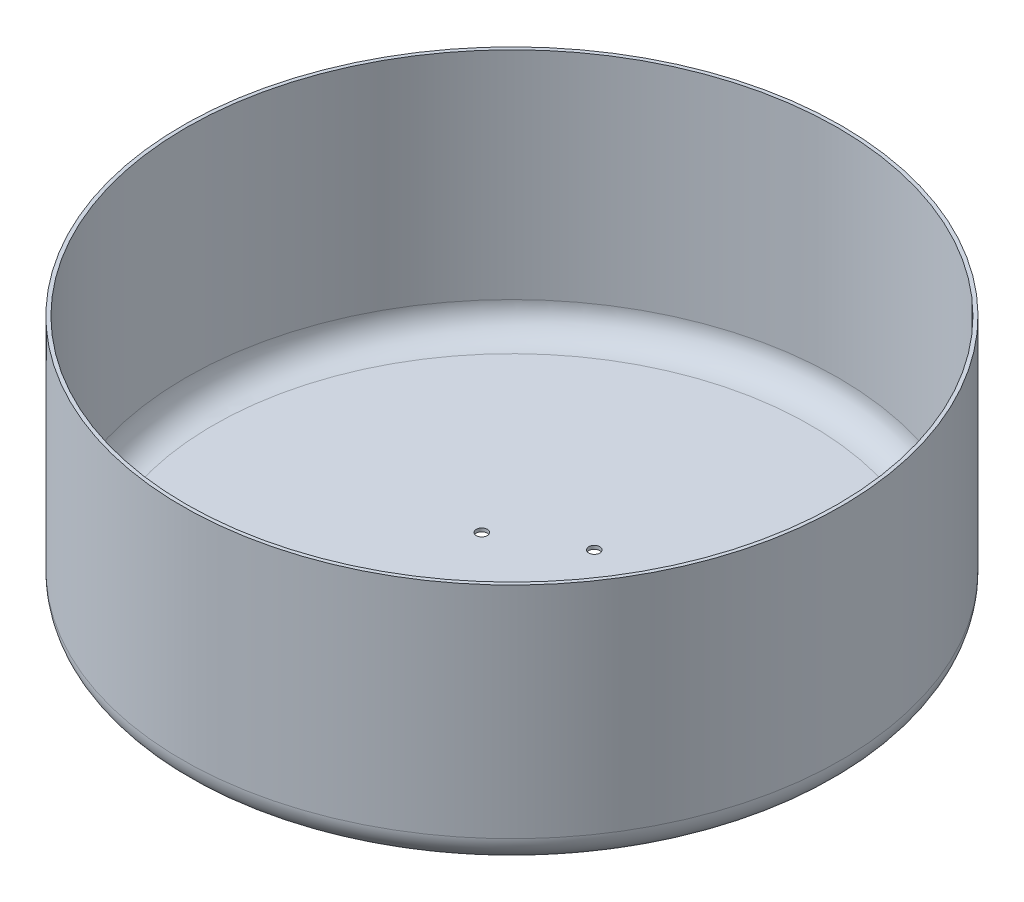
SolidWorks part; units mm, degrees
material "2024-T4"
ref_plane "Front Plane" through (0, 0, 0) normal (0, 0, 1) x (1, 0, 0)
ref_plane "Top Plane" through (0, 0, 0) normal (0, 1, 0) x (1, 0, 0)
ref_plane "Right Plane" through (0, 0, 0) normal (1, 0, 0) x (0, 0, -1)
sketch "Sketch1" plane through (0, 0, 0) normal (0, 0, 1) x (1, 0, 0)
  line L0 (0, 0) -> (0, 114.3) construction
  line L1 (0, 0) -> (152.4, 0)
  line L2 (152.4, 0) -> (152.4, 114.3)
  line L3 (152.4, 114.3) -> (150.749, 114.3)
  line L4 (150.749, 114.3) -> (150.749, 1.5748)
  line L5 (150.749, 1.5748) -> (0, 1.5748)
  line L6 (0, 1.5748) -> (0, 0)
  dimension "D1" = 114.3
  dimension "D2" = 1.5748
  dimension "D3" = 1.651
  dimension "D4" = 114.3
  dimension "D6" = 152.4
revolve "Revolve1" add sketch "Sketch1" angle 360 about L0
fillet "Fillet1" radius 12.7 2 edges at (0, 0, -152.4) (0, 1.5748, -150.749)
hole_wizard "#10 Clearance Hole1" positions "Sketch3" profile "Sketch2" hole size "#10" standard "Ansi Inch" end condition through all
sketch "Sketch3" plane through (0, 0, 0) normal (0, -1, 0) x (1, 0, 0)
  point P0 (0, 38.1)
  point P9 (32.9956, 19.05)
  point P10 (32.9956, -19.05)
  point P11 (0, -38.1)
  point P12 (-32.9956, -19.05)
  point P13 (-32.9956, 19.05)
  dimension "D1" = 38.1
  dimension "D2" = 6
sketch "Sketch2" plane through (0, 0, 38.1) normal (1, 0, 0) x (0, 0, -1)
  line L0 (0, 0) -> (0, 114.3)
  line L1 (0, 114.3) -> (2.5527, 114.3)
  line L2 (2.5527, 114.3) -> (2.5527, 0)
  line L5 (2.5527, 0) -> (0, 0)
  line L11 (0, -6.35) -> (0, 107.95) construction
  dimension "Thru Hole Dia." = 5.1054
  dimension "Thru Hole Depth" = 114.3
